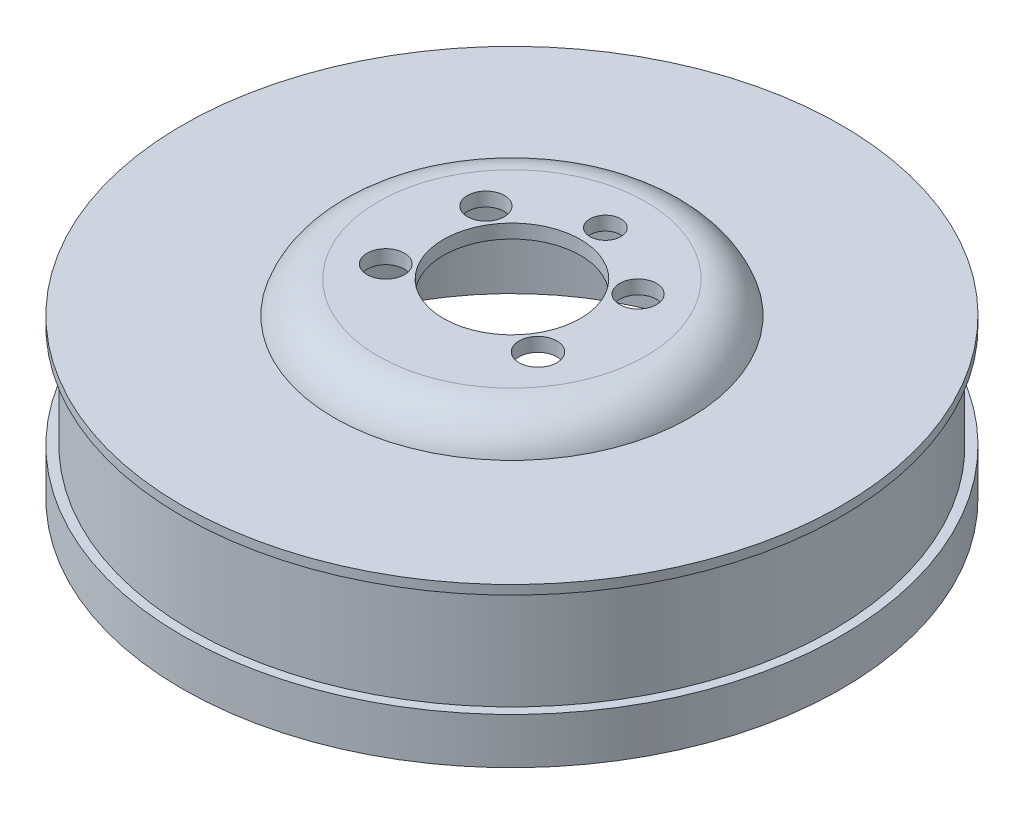
SolidWorks part; units mm, degrees
ref_plane "Alzado" through (0, 0, 0) normal (0, 0, 1) x (1, 0, 0)
ref_plane "Planta" through (0, 0, 0) normal (0, 1, 0) x (1, 0, 0)
ref_plane "Vista lateral" through (0, 0, 0) normal (1, 0, 0) x (0, 0, -1)
sketch "Croquis2" plane through (0, 0, 0) normal (0, 0, 1) x (1, 0, 0)
  line L0 (54.45, 0) -> (71.45, 0)
  line L1 (71.45, 0) -> (71.45, 10)
  line L2 (71.45, 10) -> (69.45, 10)
  line L15 (69.45, 32.4) -> (71.45, 32.4)
  line L16 (71.45, 32.4) -> (71.45, 34.4)
  line L22 (54.45, 31.4) -> (54.45, 0)
  line L23 (71.45, 34.4) -> (38.5, 34.4)
  line L24 (38.5, 34.4) -> (38.5, 41.25)
  line L29 (69.45, 32.4) -> (69.45, 10)
  line L30 (0, 41.25) -> (0, 38.25)
  line L31 (0, 38.25) -> (35.5, 38.25)
  line L32 (35.5, 38.25) -> (35.5, 31.4)
  line L33 (35.5, 31.4) -> (54.45, 31.4)
  line L34 (0, 41.25) -> (38.5, 41.25)
  point P3 (0, 0)
  point P8 (0, 0)
  dimension "D1" = 10
  dimension "D2" = 2
  dimension "D3" = 34.4
  dimension "D4" = 2
  dimension "D5" = 6.85
  dimension "D6" = 3
  dimension "D7" = 71.45
  dimension "D8" = 2
  dimension "D9" = 17
  dimension "D10" = 3
  dimension "D11" = 71.45
  dimension "D13" = 3
  dimension "D14" = 38.5
revolve "Revolución1" add sketch "Croquis2" angle 360 about L30
fillet "Redondeo2" radius 10 1 edges at (0, 41.25, 38.5)
sketch "Croquis3" plane through (0, 41.25, 0) normal (0, 1, 0) x (1, 0, 0)
  circle A0 centre (0, 0) radius 14.85
extrude "Cortar-Extruir1" cut sketch "Croquis3" against normal blind 10
sketch "Croquis4" plane through (0, 41.25, 0) normal (0, 1, 0) x (1, 0, 0)
  line L0 (16.5, 10.8541) -> (16.5, -10.8541) construction
  line L1 (-16.5, 10.8541) -> (-16.5, -10.8541) construction
  circle A0 centre (0.5184, 19.7432) radius 3.35
  circle A1 centre (0, 0) radius 14.85 construction
  circle A2 centre (0, 0) radius 19.75 construction
  circle A3 centre (-16.5, 10.8541) radius 4
  circle A4 centre (16.5, 10.8541) radius 4
  circle A5 centre (16.5, -10.8541) radius 4.1
  circle A6 centre (-16.5, -10.8541) radius 4.05
  dimension "D1" = 19.75
  dimension "D2" = 6.7
  dimension "D3" = 19.2
  dimension "D4" = 8
  dimension "D5" = 8
  dimension "D6" = 8.2
  dimension "D7" = 8.1
  dimension "D8" = 33
extrude "Cortar-Extruir2" cut sketch "Croquis4" against normal blind 10
fillet "Redondeo3" radius 10 1 edges at (0, 31.4, 35.5)
fillet "Redondeo4" radius 1 1 edges at (0, 31.4, 54.45)
